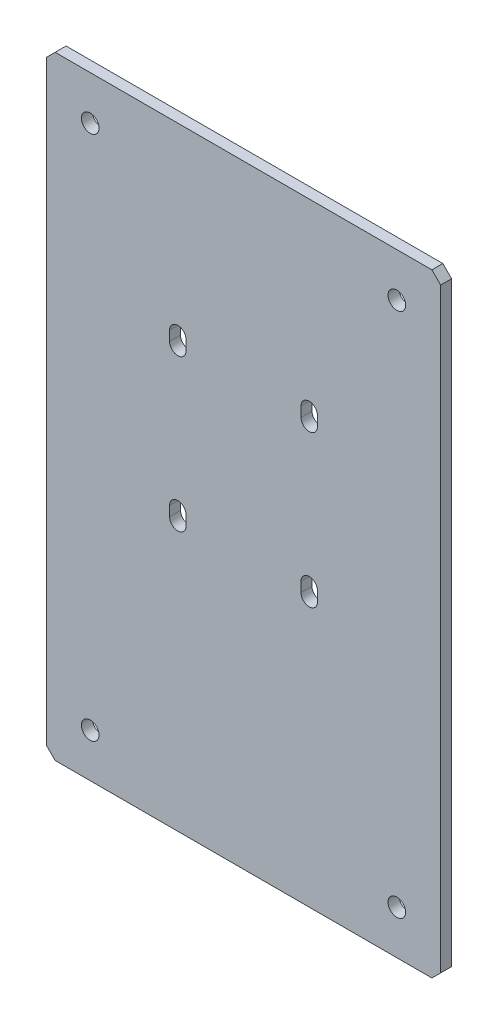
SolidWorks part; units mm, degrees
material "Acrylic (Medium-high impact)"
ref_plane "Front" through (0, 0, 0) normal (0, 0, 1) x (1, 0, 0)
ref_plane "Top" through (0, 0, 0) normal (0, 1, 0) x (1, 0, 0)
ref_plane "Right" through (0, 0, 0) normal (1, 0, 0) x (0, 0, -1)
sketch "Sketch1" plane through (0, 0, 0) normal (0, 0, 1) x (1, 0, 0)
  line L1 (0, 0) -> (114.3, 0)
  line L2 (0, 0) -> (0, 177.8)
  line L3 (0, 177.8) -> (114.3, 177.8)
  line L4 (114.3, 0) -> (114.3, 177.8)
extrude "Boss-Extrude1" add sketch "Sketch1" against normal blind 3.175
sketch "Sketch2" plane through (0, 0, 0) normal (0, 0, 1) x (1, 0, 0)
  line L0 (38.1, 121.7875) -> (38.1, 124.645) construction
  line L1 (35.7187, 121.7875) -> (35.7187, 124.645)
  line L2 (40.4813, 121.7875) -> (40.4813, 124.645)
  line L3 (38.1, 77.7875) -> (38.1, 80.645) construction
  line L4 (35.7187, 77.7875) -> (35.7187, 80.645)
  line L5 (40.4813, 77.7875) -> (40.4813, 80.645)
  line L12 (57.15, 0) -> (57.15, 21.0033) construction
  line L13 (0, 0) -> (114.3, 0) construction
  line L14 (76.2, 121.7875) -> (76.2, 124.645) construction
  line L15 (78.5813, 121.7875) -> (78.5813, 124.645)
  line L16 (73.8187, 121.7875) -> (73.8187, 124.645)
  line L17 (76.2, 77.7875) -> (76.2, 80.645) construction
  line L18 (78.5813, 77.7875) -> (78.5813, 80.645)
  line L19 (73.8187, 77.7875) -> (73.8187, 80.645)
  arc A0 (35.7187, 121.7875) -> (40.4813, 121.7875) centre (38.1, 121.7875) ccw
  arc A1 (40.4813, 124.645) -> (35.7187, 124.645) centre (38.1, 124.645) ccw
  arc A2 (35.7187, 77.7875) -> (40.4813, 77.7875) centre (38.1, 77.7875) ccw
  arc A3 (40.4813, 80.645) -> (35.7187, 80.645) centre (38.1, 80.645) ccw
  arc A8 (78.5813, 121.7875) -> (73.8187, 121.7875) centre (76.2, 121.7875) cw
  arc A9 (73.8187, 124.645) -> (78.5813, 124.645) centre (76.2, 124.645) cw
  arc A10 (78.5813, 77.7875) -> (73.8187, 77.7875) centre (76.2, 77.7875) cw
  arc A11 (73.8187, 80.645) -> (78.5813, 80.645) centre (76.2, 80.645) cw
  point P2 (38.1, 123.2162)
  point P9 (38.1, 79.2162)
  point P34 (76.2, 123.2162)
  point P41 (76.2, 79.2162)
  dimension "D2" = 7.62
  dimension "D5" = 44
  dimension "D6" = 77.7875
  dimension "D3" = 38.1
  dimension "D1" = 4.7625
extrude "Cut-Extrude1" cut sketch "Sketch2" against normal through all
sketch "Sketch5" plane through (0, 0, 0) normal (0, 0, 1) x (1, 0, 0)
  line L0 (0, 0) -> (114.3, 0) construction
  line L1 (0, 177.8) -> (0, 0) construction
  line L2 (114.3, 177.8) -> (0, 177.8) construction
  line L3 (114.3, 0) -> (114.3, 177.8) construction
  point P0 (12.7, 12.7)
  point P2 (12.7, 165.1)
  point P4 (101.6, 165.1)
  point P6 (101.6, 12.7)
  dimension "D1" = 12.7
  dimension "D2" = 12.7
  dimension "D3" = 12.7
  dimension "D4" = 12.7
hole_wizard "#10 Clearance Hole1" positions "Sketch5" profile "Sketch4" hole size "#10" standard "ANSI Inch" end condition through all
sketch "Sketch4" plane through (12.7, 12.7, 0) normal (1, 0, 0) x (0, -1, 0)
  line L0 (0, 0) -> (0, 3.175)
  line L1 (0, 3.175) -> (2.5527, 3.175)
  line L2 (2.5527, 3.175) -> (2.5527, 0)
  line L5 (2.5527, 0) -> (0, 0)
  line L11 (0, -6.35) -> (0, 107.95) construction
  dimension "Thru Hole Dia." = 5.1054
  dimension "Thru Hole Depth" = 3.175
chamfer "Chamfer1" distance 2.54 angle 45 4 edges at (0, 0, -1.5875) (114.3, 0, -1.5875) (114.3, 177.8, -1.5875) (0, 177.8, -1.5875)
